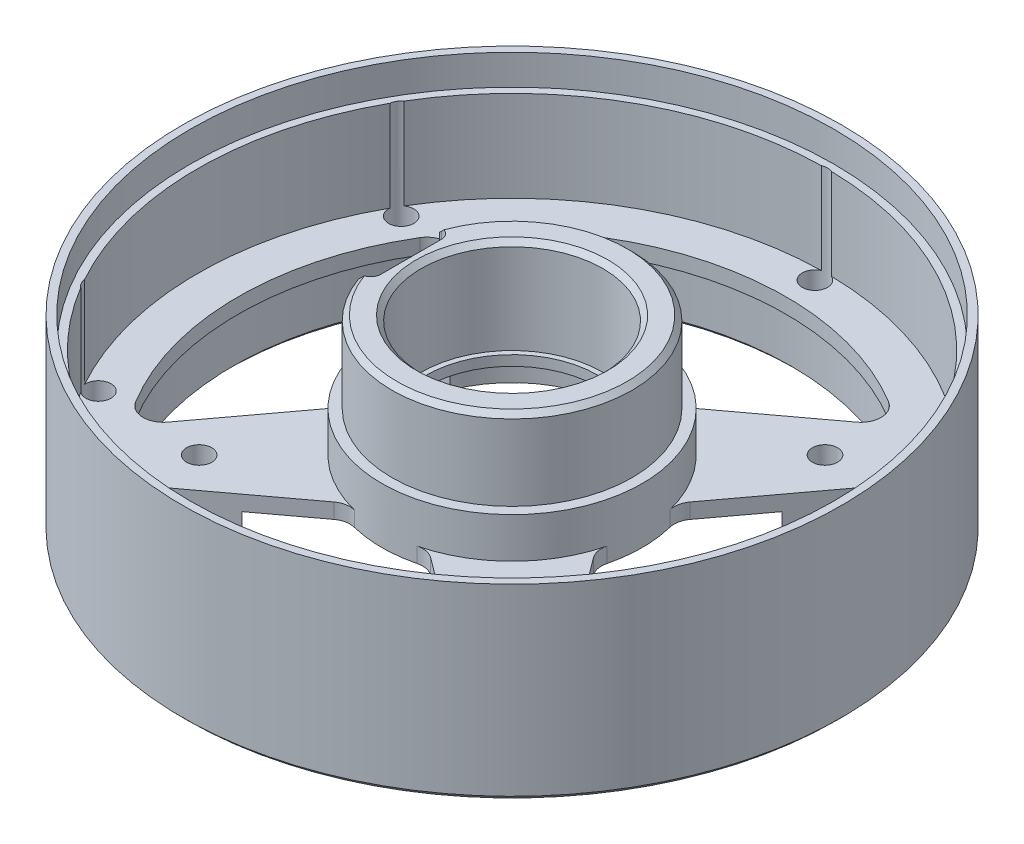
SolidWorks part; units mm, degrees
ref_plane "Front Plane" through (0, 0, 0) normal (0, 0, 1) x (1, 0, 0)
ref_plane "Top Plane" through (0, 0, 0) normal (0, 1, 0) x (1, 0, 0)
ref_plane "Right Plane" through (0, 0, 0) normal (1, 0, 0) x (0, 0, -1)
ref_axis "Axis1" through (0, 0, 0) along (0, 1, 0)
sketch "Sketch1" plane through (0, 0, 0) normal (0, 0, 1) x (1, 0, 0)
  line L0 (0, 0) -> (0, 50000) construction
  line L1 (-11.9, 4) -> (-11.9, -4)
  line L2 (-11.9, -4) -> (-12.9, -4)
  line L3 (-11.9, 4) -> (-9, 4)
  line L6 (-12, 4) -> (-12, -4) construction
  line L7 (-8.8, -5.4) -> (8.8, -5.4) construction
  line L8 (-8.5, -5.4) -> (-8.5, -6.4)
  line L12 (-25.9, -4) -> (25.9, -4) construction
  line L13 (-12.9, -4) -> (-12.9, -8)
  line L16 (-12.9, -8) -> (-31.15, -8)
  line L17 (-31.15, -8) -> (-31.15, 1)
  line L18 (-31.15, 1) -> (-31.9, 1)
  line L19 (-31.9, 1) -> (-31.9, 4)
  line L20 (-31.9, 4) -> (-32.65, 4)
  line L21 (-32.65, 4) -> (-32.65, -14.2)
  line L22 (-32.15, -14.7) -> (-27.65, -14.7)
  line L25 (-22.5, -13.7) -> (-11.5, -13.7) construction
  line L26 (-30.4, 6) -> (-30.4, -4) construction
  line L27 (-8.2505, 4) -> (-17.2973, 4) construction
  line L28 (-32.65, -14.2) -> (-32.15, -14.7)
  line L30 (-9, 4) -> (-9, -5.4)
  line L31 (-9, -5.4) -> (-8.5, -5.4)
  line L34 (-22.7479, -7) -> (22.7479, -7) construction
  line L35 (-8.5, -6.4) -> (-10.9, -6.4)
  line L38 (-10.9, -9.5) -> (-19.5, -9.5)
  line L39 (-27.65, -9.5) -> (-27.65, -14.7)
  line L40 (-24.5, -9.5) -> (-27.65, -9.5)
  line L42 (-24.5, -9.5) -> (-24.5, -12.5)
  line L43 (-24.5, -12.5) -> (-19.5, -12.5)
  line L44 (-19.5, -9.5) -> (-19.5, -12.5)
  line L47 (-10.9, -6.4) -> (-10.9, -9.5)
  dimension "D1" = 0.1
  dimension "D2" = 1
  dimension "D3" = 1
  dimension "D4" = 0.75
  dimension "D5" = 1
  dimension "D6" = 1
  dimension "D7" = 3
  dimension "D8" = 1.5
  dimension "D9" = 3
  dimension "D10" = 135
  dimension "D11" = 5
  dimension "D12" = 0.5
  dimension "D13" = 18
  dimension "D14" = 1.5
  dimension "D15" = 0.5
  dimension "D16" = 5
  dimension "D17" = 39
  dimension "D18" = 2
revolve "Revolve1" add sketch "Sketch1" angle 360 about L0
sketch "PCB outline" plane through (0, 0, 0) normal (0, 1, 0) x (1, 0, 0)
  line L4 (-22.5, 11.5) -> (-22.5, -11.5)
  line L5 (-11.5, -22.5) -> (11.5, -22.5)
  line L6 (22.5, -11.5) -> (22.5, 11.5)
  line L7 (11.5, 22.5) -> (-11.5, 22.5)
  line L8 (-22.5, 11.5) -> (-22.5, -11.5)
  line L9 (-11.5, -22.5) -> (11.5, -22.5)
  line L10 (22.5, -11.5) -> (22.5, 11.5)
  line L11 (11.5, 22.5) -> (-11.5, 22.5)
  line L12 (-12.1262, 5) -> (-28.5, 5)
  line L13 (-30.5, 3) -> (-30.5, -3)
  line L14 (-28.5, -5) -> (-12.1262, -5)
  line L15 (-12.1262, -5) -> (-12.1262, 5)
  line L16 (-12.1262, 5) -> (-28.5, 5)
  line L17 (-30.5, 3) -> (-30.5, -3)
  line L18 (-28.5, -5) -> (-12.1262, -5)
  line L19 (-12.1262, -5) -> (-12.1262, 5)
  circle A1 centre (0, 0) radius 3.5
  circle A2 centre (0, 0) radius 3.5
  circle A3 centre (-15.5, -15.5) radius 1.75
  circle A4 centre (-15.5, -15.5) radius 1.75
  circle A5 centre (15.5, -15.5) radius 1.75
  circle A6 centre (15.5, -15.5) radius 1.75
  circle A7 centre (15.5, 15.5) radius 1.75
  circle A8 centre (15.5, 15.5) radius 1.75
  circle A9 centre (-15.5, 15.5) radius 1.75
  circle A10 centre (-15.5, 15.5) radius 1.75
  arc A12 (-28.5, 5) -> (-30.5, 3) centre (-28.5, 3) ccw
  arc A13 (-30.5, -3) -> (-28.5, -5) centre (-28.5, -3) ccw
  arc A14 (-22.5, -11.5) -> (-11.5, -22.5) centre (-11.5, -11.5) ccw
  arc A15 (11.5, -22.5) -> (22.5, -11.5) centre (11.5, -11.5) ccw
  arc A16 (22.5, 11.5) -> (11.5, 22.5) centre (11.5, 11.5) ccw
  arc A17 (-11.5, 22.5) -> (-22.5, 11.5) centre (-11.5, 11.5) ccw
  arc A18 (-22.5, -11.5) -> (-11.5, -22.5) centre (-11.5, -11.5) ccw
  arc A19 (11.5, -22.5) -> (22.5, -11.5) centre (11.5, -11.5) ccw
  arc A20 (22.5, 11.5) -> (11.5, 22.5) centre (11.5, 11.5) ccw
  arc A21 (-11.5, 22.5) -> (-22.5, 11.5) centre (-11.5, 11.5) ccw
  arc A22 (-28.5, 5) -> (-30.5, 3) centre (-28.5, 3) ccw
  arc A23 (-30.5, -3) -> (-28.5, -5) centre (-28.5, -3) ccw
  dimension "D1" = 0
  dimension "D2" = 0
  dimension "D3" = 0
  dimension "D4" = 0
  dimension "D5" = 0
  dimension "D6" = 0
  dimension "D7" = 0
hole_wizard "M3x0.5 Tapped Hole2" positions "Sketch9" profile "Sketch10" tap size "M3x0.5" standard "ANSI Metric" end condition through all
sketch "Sketch9" plane through (0, -14.7, 0) normal (0, -1, 0) x (-1, 0, 0)
  circle A2 centre (0, 0) radius 30 construction
  point P60 (0, 30)
  dimension "D1" = 60
sketch "Sketch10" plane through (0, -14.7, -30) normal (1, 0, 0) x (0, 0, -1)
  line L0 (0, 0) -> (0, 18.7)
  line L1 (0, 18.7) -> (1.25, 18.7)
  line L2 (1.25, 18.7) -> (1.25, 0)
  line L5 (1.25, 0) -> (0, 0)
  line L11 (0, -6.35) -> (0, 107.95) construction
  dimension "Thru Tap Drill Dia." = 2.5
  dimension "Thru Tap Drill Depth" = 18.7
cosmetic thread "Hole Thread5" parameters "D2"=3
hole_wizard "M3x0.5 Tapped Hole3" positions "Sketch11" profile "Sketch12" tap size "M3x0.5" standard "ANSI Metric" end condition through all
sketch "Sketch11" plane through (0, -12.5, 0) normal (0, -1, 0) x (-1, 0, 0)
  point P0 (-15.5, 15.5)
  point P3 (15.5, 15.5)
  point P6 (-15.5, -15.5)
  point P9 (15.5, -15.5)
sketch "Sketch12" plane through (15.5, -12.5, -15.5) normal (1, 0, 0) x (0, 0, -1)
  line L0 (0, 0) -> (0, 16.5)
  line L1 (0, 16.5) -> (1.25, 16.5)
  line L2 (1.25, 16.5) -> (1.25, 0)
  line L5 (1.25, 0) -> (0, 0)
  line L11 (0, -6.35) -> (0, 107.95) construction
  dimension "Thru Tap Drill Dia." = 2.5
  dimension "Thru Tap Drill Depth" = 16.5
cosmetic thread "Hole Thread13" parameters "D2"=3
cosmetic thread "Hole Thread14" parameters "D2"=3
cosmetic thread "Hole Thread15" parameters "D2"=3
cosmetic thread "Hole Thread16" parameters "D2"=3
sketch "Sketch13" plane through (0, 0, 0) normal (0, 1, 0) x (1, 0, 0)
  line L0 (14.2523, 19.8892) -> (4.7929, 12.8539)
  line L1 (0, 0) -> (0, 34.2944) construction
  line L2 (-14.2523, 19.8892) -> (-4.7929, 12.8539)
  arc A0 (-3.1162, 12.518) -> (3.1162, 12.518) centre (0, 0) cw
  arc A1 (-14.0972, 23.2033) -> (14.0972, 23.2033) centre (0, 0) cw
  circle A2 centre (0, 0) radius 31.15 construction
  circle A3 centre (0, 0) radius 12.9 construction
  arc A4 (-3.1162, 12.518) -> (-4.7929, 12.8539) centre (-3.5994, 14.4587) cw
  arc A5 (3.1162, 12.518) -> (4.7929, 12.8539) centre (3.5994, 14.4587) ccw
  arc A6 (14.0972, 23.2033) -> (14.2523, 19.8892) centre (13.0587, 21.494) cw
  arc A7 (-14.0972, 23.2033) -> (-14.2523, 19.8892) centre (-13.0587, 21.494) ccw
  point P16 (-4, 12.2642)
  point P19 (4, 12.2642)
  point P22 (16.5, 21.5609)
  point P25 (-16.5, 21.5609)
  dimension "D1" = 4
  dimension "D2" = 8
  dimension "D4" = 2
  dimension "D3" = 33
extrude "Cut-Extrude4" cut sketch "Sketch13" against normal through all
pattern_circular "CirPattern3" count 4 over 360 about axis through (0, 0, 0) along (0, 1, 0) of "Cut-Extrude4"
sketch "Sketch14" plane through (0, 0, 0) normal (0, 1, 0) x (1, 0, 0)
  line L0 (-30.5, 3) -> (-30.5, -3) construction
  line L1 (-19.3399, 5.5) -> (-28.75, 5.5)
  line L2 (-19.3399, 5.5) -> (-19.3399, -5.5)
  line L3 (-19.3399, -5.5) -> (-28.75, -5.5)
  line L4 (-30.75, 3.5) -> (-30.75, -3.5)
  arc A0 (-28.75, -5.5) -> (-30.75, -3.5) centre (-28.75, -3.5) cw
  arc A1 (-28.75, 5.5) -> (-30.75, 3.5) centre (-28.75, 3.5) ccw
  point P4 (-19.3399, 0)
  dimension "D2" = 2
  dimension "D1" = 11
  dimension "D3" = 0.25
extrude "Cut-Extrude5" [suppressed] cut sketch "Sketch14" against normal through all
pattern_circular "CirPattern4" count 6 over 360 about axis through (0, 0, 0) along (0, 1, 0) of "M3x0.5 Tapped Hole2"
chamfer "Chamfer1" distance 0.5 angle 45 3 edges at (0, -14.7, -27.65) (0, 4, -11.9) (0, 4, -9)
sketch "Sketch16" plane through (0, 0, 0) normal (0, 1, 0) x (1, 0, 0)
  line L1 (-18.7697, 4) -> (-11, 4)
  line L2 (-19.7697, 3) -> (-19.7697, -3)
  line L3 (-18.7697, -4) -> (-11, -4)
  line L4 (-10, 3) -> (-10, -3)
  arc A0 (-11, 4) -> (-10, 3) centre (-11, 3) cw
  arc A1 (-19.7697, -3) -> (-18.7697, -4) centre (-18.7697, -3) ccw
  arc A2 (-11, -4) -> (-10, -3) centre (-11, -3) ccw
  arc A3 (-18.7697, 4) -> (-19.7697, 3) centre (-18.7697, 3) ccw
  circle A5 centre (0, 0) radius 9 construction
  circle A6 centre (0, 0) radius 9 construction
  point P12 (-10, 0)
  point P14 (-9, 0)
  dimension "D1" = 1
  dimension "D2" = 8
  dimension "D3" = 1
extrude "Cut-Extrude6" cut sketch "Sketch16" against normal through all both and the other way through all
sketch "Sketch18" plane through (0, 0, 0) normal (0, 1, 0) x (1, 0, 0)
  line L0 (-18.7697, 4) -> (-11, 4) construction
  line L1 (-18.1379, 4) -> (-4.3342, 4)
  line L2 (-18.1379, 4) -> (-18.1379, -4)
  line L3 (-18.1379, -4) -> (-4.3342, -4)
  line L4 (-4.3342, 4) -> (-4.3342, -4)
  line L5 (-18.7697, -4) -> (-11, -4) construction
extrude "Cut-Extrude7" cut sketch "Sketch18" against normal through all from surface starting at face at (0, -6.4, -8.5)
